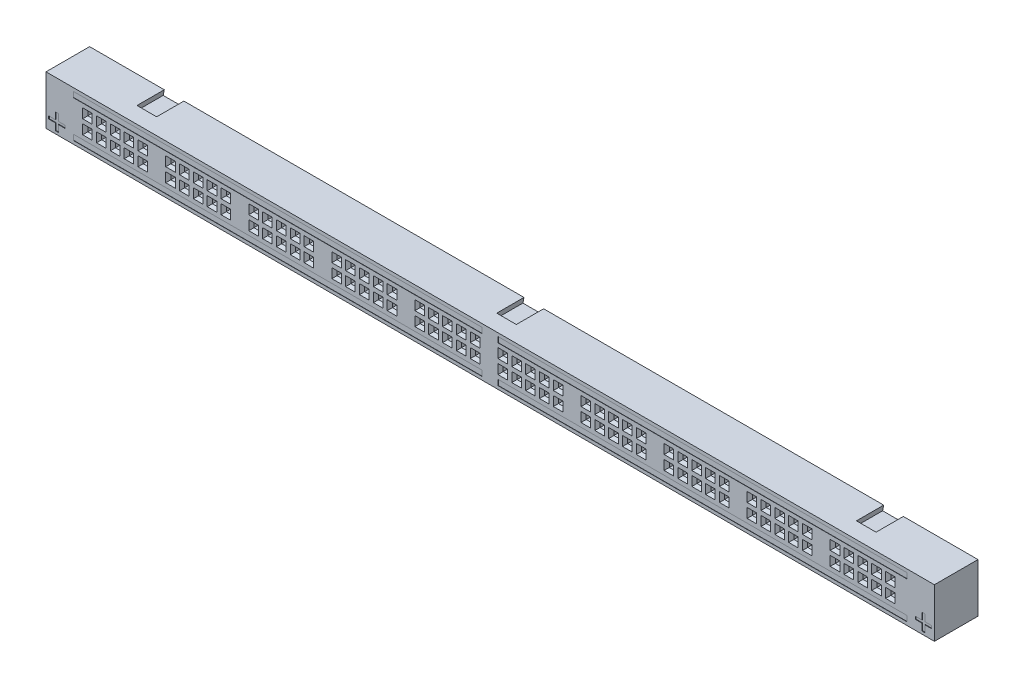
SolidWorks part; units mm, degrees
ref_plane "Front Plane" through (0, 0, 0) normal (0, 0, 1) x (1, 0, 0)
ref_plane "Top Plane" through (0, 0, 0) normal (0, 1, 0) x (1, 0, 0)
ref_plane "Right Plane" through (0, 0, 0) normal (1, 0, 0) x (0, 0, -1)
sketch "Sketch1" plane through (0, 0, 0) normal (0, 0, 1) x (1, 0, 0)
  line L1 (0, 0) -> (163, 0)
  line L2 (0, 0) -> (0, 9)
  line L3 (0, 9) -> (163, 9)
  line L4 (163, 0) -> (163, 9)
  dimension "D1" = 163
  dimension "D2" = 9
extrude "Boss-Extrude1" add sketch "Sketch1" along normal blind 8
sketch "Sketch2" plane through (0, 0, 8) normal (0, 0, 1) x (1, 0, 0)
  line L0 (163, 0) -> (163, 9) construction
  line L1 (163, 0) -> (163, 9)
  line L2 (154.92, 0) -> (154.92, 9) construction
  line L3 (154.92, 4.5) -> (159.3402, 4.5) construction
  line L5 (154.92, 5.77) -> (159.3402, 5.77) construction
  line L6 (154.045, 6.645) -> (155.795, 6.645)
  line L7 (154.045, 6.645) -> (154.045, 4.895)
  line L8 (154.045, 4.895) -> (155.795, 4.895)
  line L9 (155.795, 6.645) -> (155.795, 4.895)
  line L10 (154.045, 6.645) -> (155.795, 4.895) construction
  line L11 (154.045, 4.895) -> (155.795, 6.645) construction
  line L16 (154.52, 5.37) -> (155.32, 6.17) construction
  line L17 (154.52, 6.17) -> (155.32, 5.37) construction
  dimension "D2" = 1.75
  dimension "D1" = 8.08
  dimension "D3" = 1.27
extrude "Cut-Extrude1" cut sketch "Sketch2" against normal blind 8 draft 45 contours L9 L6 L7 L8
sketch "Sketch3" plane through (0, 0, 8) normal (0, 0, 1) x (1, 0, 0)
  line L0 (154.045, 4.895) -> (155.795, 6.645) construction
  line L2 (154.52, 5.37) -> (155.32, 5.37)
  line L3 (154.52, 5.37) -> (154.52, 6.17)
  line L4 (154.52, 6.17) -> (155.32, 6.17)
  line L5 (155.32, 5.37) -> (155.32, 6.17)
  line L6 (154.52, 5.37) -> (155.32, 6.17) construction
  line L7 (154.52, 6.17) -> (155.32, 5.37) construction
  point P4 (154.92, 5.77)
extrude "Cut-Extrude2" cut sketch "Sketch3" against normal blind 5
ref_plane "Plane1" through (0, 4.5, 0) normal (0, -1, 0) x (-1, 0, 0)
mirror "Mirror1" about plane through (0, 4.5, 0) normal (0, -1, 0) of "Cut-Extrude2", "Cut-Extrude1"
pattern_linear "LPattern1" count 5 spacing 2.54 along (-1, 0, 0) of "Cut-Extrude2", "Cut-Extrude1", "Mirror1"
pattern_linear "LPattern2" count 10 spacing 15.24 along (-1, 0, 0) of "LPattern1", "Cut-Extrude1", "Cut-Extrude2", "Mirror1"
sketch "Sketch4" plane through (0, 0, 8) normal (0, 0, 1) x (1, 0, 0)
  line L0 (0, 0) -> (163, 0) construction
  line L1 (80.0399, 1.6) -> (5.0399, 1.6)
  line L2 (80.0399, 1.6) -> (80.0399, 0.6)
  line L3 (80.0399, 0.6) -> (5.0399, 0.6)
  line L4 (5.0399, 1.6) -> (5.0399, 0.6)
  dimension "D1" = 75
  dimension "D2" = 1
  dimension "D3" = 0.6
extrude "Cut-Extrude3" cut sketch "Sketch4" against normal blind 0.05
mirror "Mirror2" about plane through (0, 4.5, 0) normal (0, -1, 0) of "Cut-Extrude3"
ref_plane "Plane2" through (81.5, 0, 0) normal (-1, 0, 0) x (0, 0, 1)
mirror "Mirror3" about plane through (81.5, 0, 0) normal (-1, 0, 0) of "Cut-Extrude3", "Mirror2"
sketch "Sketch5" plane through (0, 0, 0) normal (0, 0, -1) x (-1, 0, 0)
  line L0 (-81.5, 0) -> (-81.5, -1) construction
  line L1 (0, 0) -> (-163, 0) construction
  line L2 (-79.7, 0) -> (-83.3, 0)
  line L3 (-79.5, -1) -> (-83.5, -1)
  line L4 (-83.5, -1) -> (-83.3, 0)
  line L5 (-79.5, -1) -> (-79.7, 0)
  point P7 (-81.5, 0)
  point P10 (-81.5, -1)
  dimension "D1" = 1
  dimension "D2" = 4
  dimension "D3" = 3.6
extrude "Boss-Extrude2" add sketch "Sketch5" against normal blind 5
pattern_linear "LPattern3" count 2 spacing 66 along (-1, 0, 0) count 2 spacing 66 along (1, 0, 0) of "Boss-Extrude2"
sketch "Sketch6" plane through (0, 0, 0) normal (0, 0, -1) x (-1, 0, 0)
  line L0 (-15.5, -1) -> (-15.5, 9) construction
  line L1 (-17.5, -1) -> (-13.5, -1) construction
  line L2 (-163, 9) -> (0, 9) construction
  line L3 (-13.7, 9) -> (-17.3, 9)
  line L4 (-13.5, 8) -> (-17.5, 8)
  line L5 (-13.7, 9) -> (-13.5, 8)
  line L6 (-17.5, 8) -> (-17.3, 9)
  point P9 (-15.5, 9)
  point P12 (-15.5, 8)
  dimension "D1" = 1
extrude "Cut-Extrude4" cut sketch "Sketch6" against normal blind 5
pattern_linear "LPattern4" count 3 spacing 66 along (1, 0, 0) of "Cut-Extrude4"
sketch "Sketch7" plane through (0, 0, 8) normal (0, 0, 1) x (1, 0, 0)
  line L0 (1.75, 3.5) -> (2.25, 0.5) construction
  line L1 (1.75, 3.5) -> (2.25, 3.5)
  line L2 (1.75, 3.5) -> (1.75, 2.25)
  line L3 (1.75, 0.5) -> (2.25, 0.5)
  line L4 (2.25, 3.5) -> (2.25, 2.25)
  line L5 (2.25, 2.25) -> (3.5, 2.25)
  line L6 (0.5, 2.25) -> (1.75, 2.25)
  line L7 (0.5, 2.25) -> (0.5, 1.75)
  line L8 (0.5, 1.75) -> (1.75, 1.75)
  line L9 (3.5, 2.25) -> (3.5, 1.75)
  line L10 (0.5, 2.25) -> (3.5, 1.75) construction
  line L11 (0.5, 1.75) -> (3.5, 2.25) construction
  line L12 (1.75, 1.75) -> (1.75, 0.5)
  line L13 (0, 9) -> (0, 0) construction
  line L14 (2.25, 1.75) -> (3.5, 1.75)
  line L15 (2.25, 1.75) -> (2.25, 0.5)
  line L16 (0, 0) -> (163, 0) construction
  point P4 (2, 2)
  dimension "D1" = 0.5
  dimension "D2" = 1.25
  dimension "D3" = 0.5
  dimension "D4" = 0.5
extrude "Cut-Extrude5" cut sketch "Sketch7" against normal blind 0.1
mirror "Mirror4" about plane through (81.5, 0, 0) normal (-1, 0, 0) of "Cut-Extrude5"
